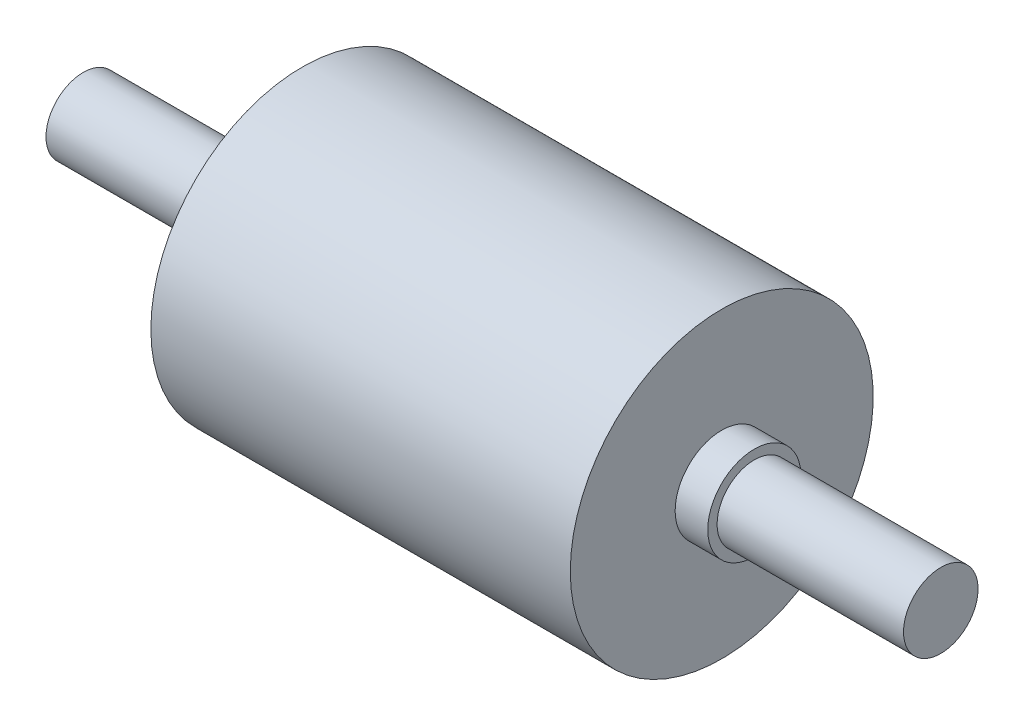
SolidWorks part; units mm, degrees
ref_plane "Ön Düzlem" through (0, 0, 0) normal (0, 0, 1) x (1, 0, 0)
ref_plane "Üst Düzlem" through (0, 0, 0) normal (0, 1, 0) x (1, 0, 0)
ref_plane "Sağ Düzlem" through (0, 0, 0) normal (1, 0, 0) x (0, 0, -1)
sketch "Çizim1" plane through (0, 0, 0) normal (0, 0, 1) x (1, 0, 0)
  line L0 (0, 0) -> (0, 4)
  line L1 (0, 4) -> (20, 4)
  line L2 (20, 4) -> (20, 5)
  line L3 (20, 5) -> (23.5, 5)
  line L4 (23.5, 5) -> (23.5, 16.25)
  line L5 (23.5, 16.25) -> (68.5, 16.25)
  line L6 (68.5, 16.25) -> (68.5, 5)
  line L7 (68.5, 5) -> (72, 5)
  line L8 (72, 5) -> (72, 4)
  line L9 (72, 4) -> (92, 4)
  line L10 (92, 4) -> (92, 0)
  line L11 (0, 0) -> (50000, 0) construction
  line L12 (0, 0) -> (92, 0)
revolve "Döndür1" add sketch "Çizim1" angle 360 about L11
